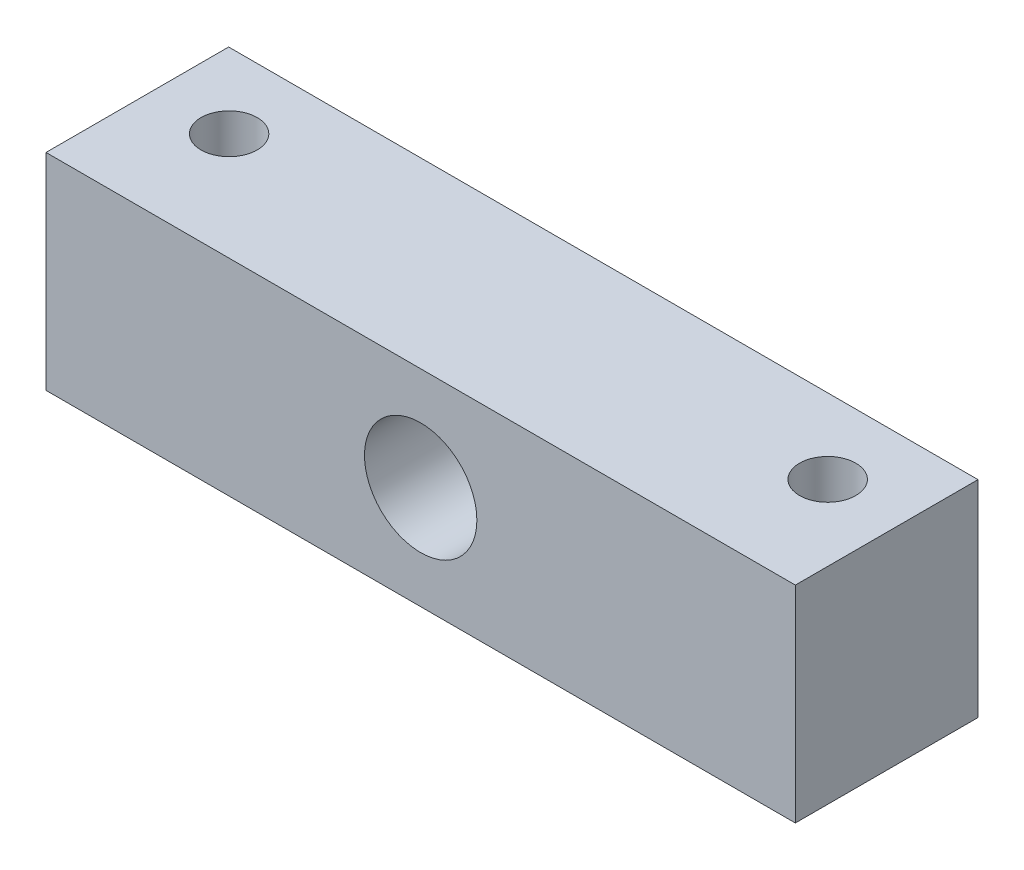
SolidWorks part; units mm, degrees
ref_plane "Front" through (0, 0, 0) normal (0, 0, 1) x (1, 0, 0)
ref_plane "Top" through (0, 0, 0) normal (0, 1, 0) x (1, 0, 0)
ref_plane "Right" through (0, 0, 0) normal (1, 0, 0) x (0, 0, -1)
sketch "Sketch1" plane through (0, 0, 0) normal (0, 1, 0) x (1, 0, 0)
  line L0 (-20, 0) -> (20, 0) construction
  line L1 (20, -4.875) -> (-20, -4.875)
  line L2 (20, -4.875) -> (20, 4.875)
  line L3 (20, 4.875) -> (-20, 4.875)
  line L4 (-20, -4.875) -> (-20, 4.875)
  line L5 (20, -4.875) -> (-20, 4.875) construction
  line L6 (20, 4.875) -> (-20, -4.875) construction
  line L7 (0, 4.875) -> (0, -4.875) construction
  circle A0 centre (-15.9761, 0.875) radius 1.5
  circle A1 centre (15.9761, 0.875) radius 1.5
  point P0 (0, 0)
  dimension "D3" = 3
  dimension "D1" = 40
  dimension "D2" = 9.75
  dimension "D4" = 16
  dimension "D5" = 4
extrude "Boss-Extrude1" add sketch "Sketch1" along normal blind 11
sketch "Sketch2" plane through (0, 0, 4.875) normal (0, 0, 1) x (1, 0, 0)
  line L0 (0, 11) -> (0, 0) construction
  line L1 (-20, 11) -> (20, 11) construction
  line L2 (-20, 0) -> (20, 0) construction
  line L3 (20, 11) -> (20, 0) construction
  circle A0 centre (0, 5.5) radius 3
  circle A1 centre (8.5966, 4.0126) radius 1.5
  circle A2 centre (-8.5966, 4.0126) radius 1.5
  point P10 (20, 5.5)
  dimension "D1" = 6
  dimension "D3" = 3
  dimension "D2" = 11.5
extrude "Cut-Extrude1" cut sketch "Sketch2" against normal up to next contours L0 A0 | A0 L0 region at (1.2732, 5.5, 4.875) region at (-1.2732, 5.5, 4.875)
